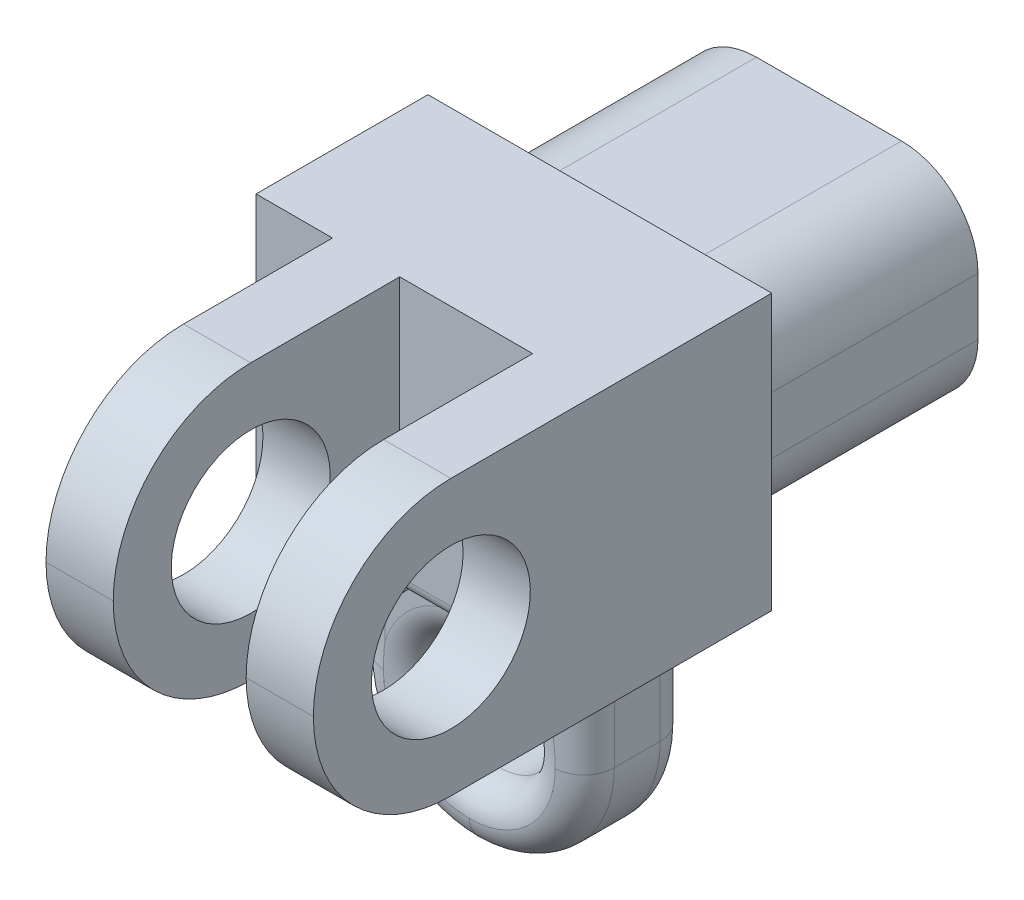
SolidWorks part; units mm, degrees
ref_plane "Plan de face" through (0, 0, 0) normal (0, 0, 1) x (1, 0, 0)
ref_plane "Plan de dessus" through (0, 0, 0) normal (0, 1, 0) x (1, 0, 0)
ref_plane "Plan de droite" through (0, 0, 0) normal (1, 0, 0) x (0, 0, -1)
sketch "Sketch2" plane through (0, 0, 0) normal (0, 0, 1) x (1, 0, 0)
  line L1 (12.3825, -8.7312) -> (-12.3825, -8.7312)
  line L2 (12.3825, -8.7312) -> (12.3825, 8.7313)
  line L3 (12.3825, 8.7313) -> (-12.3825, 8.7312)
  line L4 (-12.3825, -8.7312) -> (-12.3825, 8.7312)
  line L5 (12.3825, -8.7312) -> (-12.3825, 8.7312) construction
  line L6 (12.3825, 8.7313) -> (-12.3825, -8.7312) construction
  point P0 (0, 0)
  dimension "D1" = 24.765
  dimension "D2" = 17.4625
extrude "Boss-Extrude1" add sketch "Sketch2" against normal blind 19.05
sketch "Sketch3" plane through (0, 0, 0) normal (0, 0, 1) x (1, 0, 0)
  line L1 (14.2875, -11.43) -> (-14.2875, -11.43)
  line L2 (14.2875, -11.43) -> (14.2875, 11.43)
  line L3 (14.2875, 11.43) -> (-14.2875, 11.43)
  line L4 (-14.2875, -11.43) -> (-14.2875, 11.43)
  line L5 (14.2875, -11.43) -> (-14.2875, 11.43) construction
  line L6 (14.2875, 11.43) -> (-14.2875, -11.43) construction
  point P0 (0, 0)
  dimension "D1" = 28.575
  dimension "D2" = 22.86
extrude "Boss-Extrude2" add sketch "Sketch3" along normal blind 38.1
sketch "Sketch4" plane through (0, -11.43, 0) normal (0, -1, 0) x (-1, 0, 0)
  line L0 (14.2875, -38.1) -> (-14.2875, -38.1) construction
  line L1 (14.2875, -38.1) -> (7.9375, -38.1)
  line L2 (14.2875, -38.1) -> (14.2875, -14.2875)
  line L3 (14.2875, -14.2875) -> (7.9375, -14.2875)
  line L4 (7.9375, -38.1) -> (7.9375, -14.2875)
  line L5 (2.3495, -38.1) -> (-8.6995, -38.1)
  line L6 (2.3495, -38.1) -> (2.3495, -14.2875)
  line L7 (2.3495, -14.2875) -> (-8.6995, -14.2875)
  line L8 (-8.6995, -38.1) -> (-8.6995, -14.2875)
  line L9 (-14.2875, -38.1) -> (-14.2875, 0) construction
  dimension "D1" = 23.8125
  dimension "D2" = 23.8125
  dimension "D3" = 6.35
  dimension "D4" = 5.588
  dimension "D5" = 5.588
extrude "Cut-Extrude1" cut sketch "Sketch4" against normal through all
sketch "Sketch5" plane through (0, -11.43, 0) normal (0, -1, 0) x (1, 0, 0)
  line L0 (-14.2875, 0) -> (14.2875, 0) construction
  line L1 (-9.525, 10.8585) -> (9.525, 10.8585)
  line L2 (-9.525, 10.8585) -> (-9.525, 1.9685)
  line L3 (-9.525, 1.9685) -> (9.525, 1.9685)
  line L4 (9.525, 10.8585) -> (9.525, 1.9685)
  line L5 (-14.2875, 14.2875) -> (-14.2875, 0) construction
  point P6 (-9.525, 6.4135)
  dimension "D1" = 8.89
  dimension "D2" = 1.9685
  dimension "D3" = 19.05
  dimension "D4" = 4.7625
extrude "Boss-Extrude3" add sketch "Sketch5" along normal blind 19.05
fillet "Fillet1" radius 9.525 2 edges at (9.525, -30.48, 6.4135) (-9.525, -30.48, 6.4135)
sketch "Sketch6" plane through (0, 0, 1.9685) normal (0, 0, -1) x (-1, 0, 0)
  line L0 (0, -20.955) -> (0, -11.43) construction
  line L1 (9.525, -11.43) -> (-9.525, -11.43) construction
  line L2 (0, -20.955) -> (0, -30.48) construction
  circle A1 centre (0, -20.955) radius 4.7625
  dimension "D1" = 9.525
extrude "Cut-Extrude2" cut sketch "Sketch6" against normal through all
fillet "Fillet5" radius 11.43 4 edges at (-5.1435, -11.43, 38.1) (-5.1435, 11.43, 38.1) (11.4935, 11.43, 38.1) (11.4935, -11.43, 38.1)
sketch "Sketch7" plane through (-7.9375, 0, 0) normal (-1, 0, 0) x (0, 0, 1)
  circle A1 centre (26.67, 0) radius 6.604
  dimension "D1" = 13.208
extrude "Cut-Extrude3" cut sketch "Sketch7" against normal through all
fillet "Fillet2" radius 2.54 10 edges at (-4.7625, -20.955, 1.9685) (-4.7625, -20.955, 10.8585) (9.525, -16.1925, 1.9685) (-9.525, -16.1925, 1.9685) (-6.7352, -27.6902, 1.9685) (-9.525, -16.1925, 10.8585) (-6.7352, -27.6902, 10.8585) (9.525, -16.1925, 10.8585) (6.7352, -27.6902, 1.9685) (6.7352, -27.6902, 10.8585)
fillet "Fillet3" radius 6.35 4 edges at (-12.3825, -8.7312, -9.525) (-12.3825, 8.7312, -9.525) (12.3825, -8.7312, -9.525) (12.3825, 8.7313, -9.525)
fillet "Fillet6" radius 1.27 2 edges at (-11.1125, -11.43, 14.2875) (3.175, -11.43, 14.2875)
